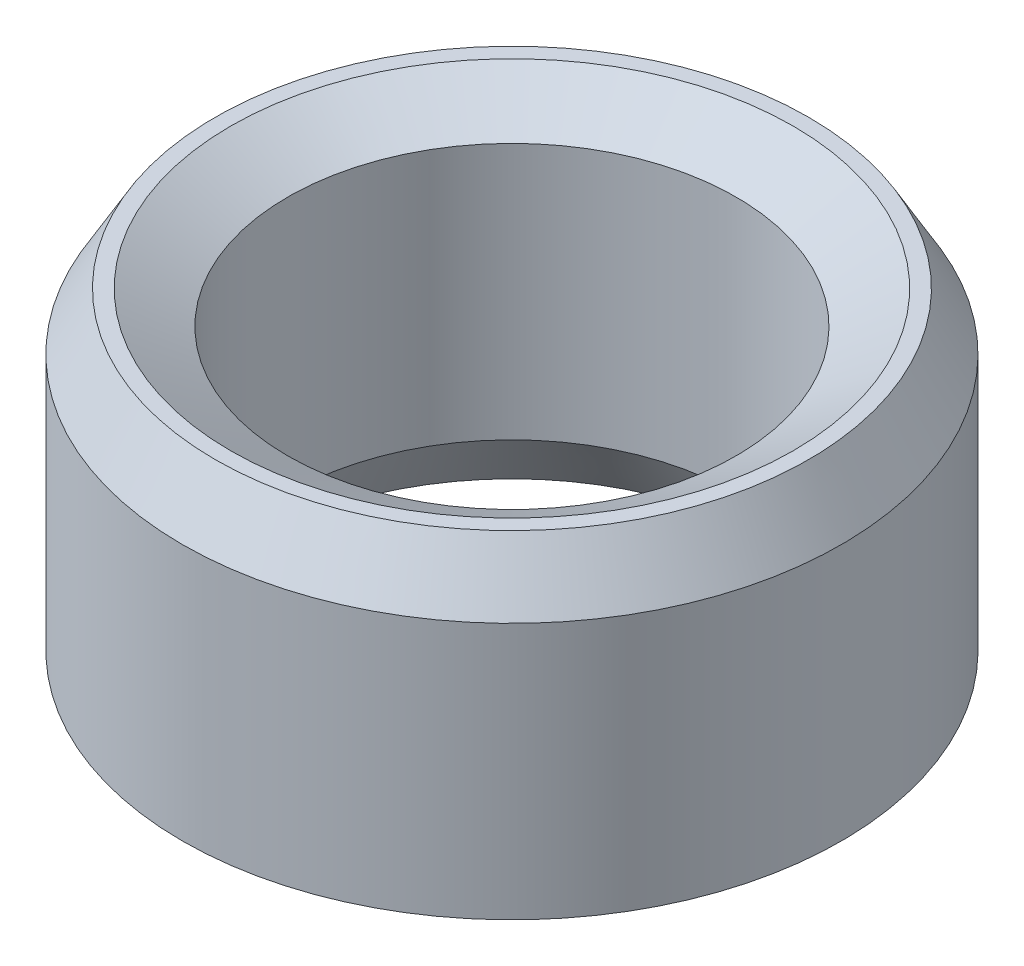
SolidWorks part; units mm, degrees
ref_plane "Front Plane" through (0, 0, 0) normal (0, 0, 1) x (1, 0, 0)
ref_plane "Top Plane" through (0, 0, 0) normal (0, 1, 0) x (1, 0, 0)
ref_plane "Right Plane" through (0, 0, 0) normal (1, 0, 0) x (0, 0, -1)
sketch "Sketch1" plane through (0, 0, 0) normal (0, 1, 0) x (1, 0, 0)
  circle A0 centre (0, 0) radius 10
  dimension "SLEEVE_OD" = 20
extrude "Boss-Extrude1" add sketch "Sketch1" along normal blind 10.5202
sketch "Sketch2" plane through (0, 0, 0) normal (0, 1, 0) x (1, 0, 0)
  circle A0 centre (0, 0) radius 6.8033
  dimension "BORE_D" = 13.6065
extrude "Cut-Extrude1" cut sketch "Sketch2" along normal through all
chamfer "Chamfer1" distance 1.7309 angle 30 4 edges at (0, 10.5202, 6.8033) (0, 0, 6.8033) (0, 0, 10) (0, 10.5202, 10) first distance on face at (0, 10.5202, 6.8033) first distance on face at (0, 0, 6.8033) first distance on face at (0, 10.5202, 10)
